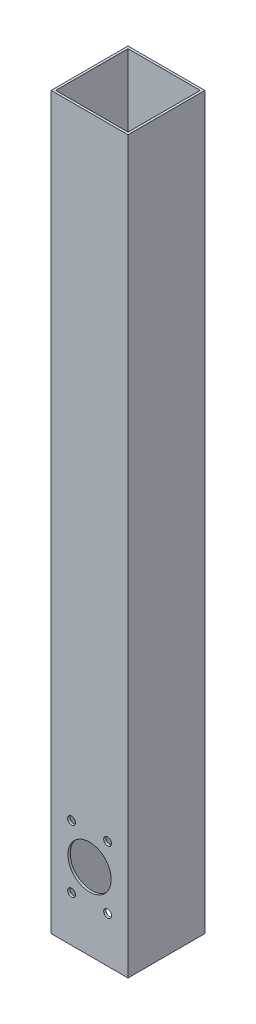
SolidWorks part; units mm, degrees
material "6061 Alloy"
ref_plane "Front Plane" through (0, 0, 0) normal (0, 0, 1) x (1, 0, 0)
ref_plane "Top Plane" through (0, 0, 0) normal (0, 1, 0) x (1, 0, 0)
ref_plane "Right Plane" through (0, 0, 0) normal (1, 0, 0) x (0, 0, -1)
sketch "Sketch1" plane through (0, 0, 0) normal (0, 1, 0) x (1, 0, 0)
  line L1 (25.4, 25.4) -> (-25.4, 25.4)
  line L2 (25.4, 25.4) -> (25.4, -25.4)
  line L3 (25.4, -25.4) -> (-25.4, -25.4)
  line L4 (-25.4, 25.4) -> (-25.4, -25.4)
  line L5 (25.4, 25.4) -> (-25.4, -25.4) construction
  line L6 (25.4, -25.4) -> (-25.4, 25.4) construction
  point P0 (0, 0)
  dimension "D1" = 50.8
extrude "Extrude-Thin1" add sketch "Sketch1" along normal blind 482.6 thin thin type one direction reverse wall 1.524
sketch "Sketch2" plane through (0, 0, 0) normal (0, 0, 1) x (1, 0, 0)
  line L0 (-36.2563, 68.2625) -> (38.5702, 68.2625) construction
  line L1 (-25.4, 0) -> (25.4, 0) construction
  line L2 (-25.4, 50.8) -> (25.4, 50.8) construction
  line L6 (25.4, 482.6) -> (25.4, 0) construction
  line L7 (-25.4, 482.6) -> (-25.4, 0) construction
  line L8 (-11.9126, 30.1668) -> (11.9126, 30.1668) construction
  line L9 (-11.9126, 71.4332) -> (11.9126, 71.4332) construction
  circle A0 centre (0, 50.8) radius 14.3002
  circle A1 centre (0, 50.8) radius 23.8252 construction
  circle A2 centre (-11.9126, 30.1668) radius 2.5908
  circle A3 centre (11.9126, 30.1668) radius 2.5908
  circle A4 centre (11.9126, 71.4332) radius 2.5908
  circle A5 centre (-11.9126, 71.4332) radius 2.5908
  point P11 (0, 50.8)
  dimension "D1" = 28.6004
  dimension "D3" = 17.4625
  dimension "D4" = 47.6504
  dimension "D6" = 5.1816
  dimension "D2" = 50.8
  dimension "D5" = 23.8252
extrude "Cut-Extrude1" cut sketch "Sketch2" along normal through all both and the other way through all
